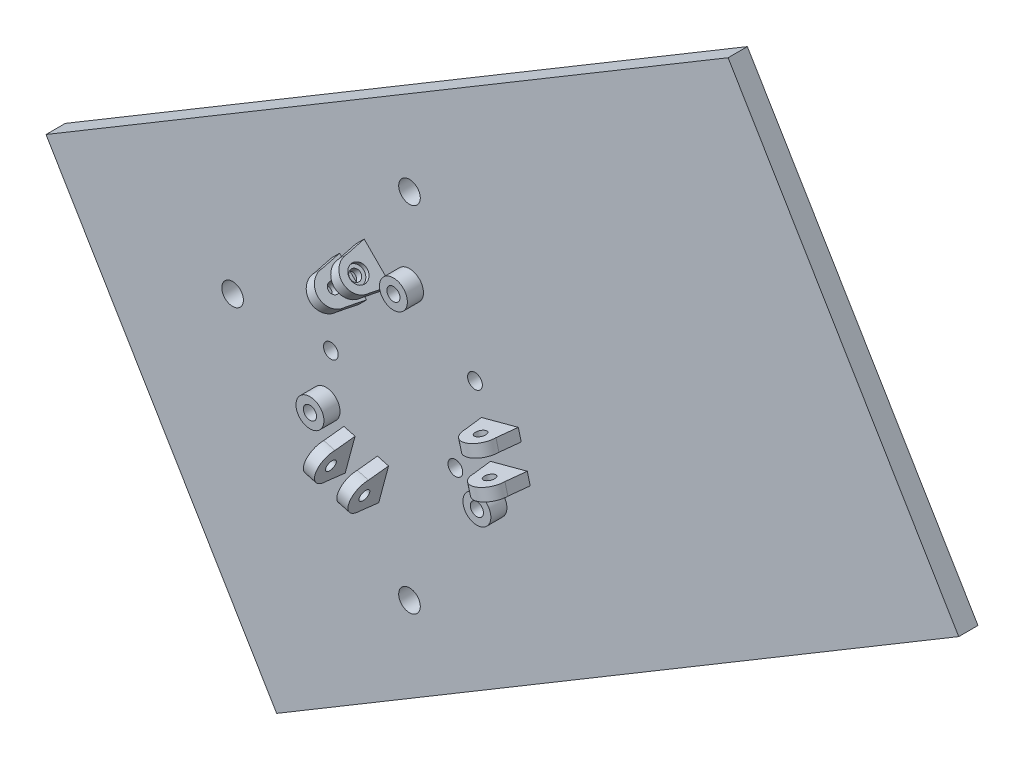
SolidWorks part; units mm, degrees
ref_plane "Front Plane" through (0, 0, 0) normal (0, 0, 1) x (1, 0, 0)
ref_plane "Top Plane" through (0, 0, 0) normal (0, 1, 0) x (1, 0, 0)
ref_plane "Right Plane" through (0, 0, 0) normal (1, 0, 0) x (0, 0, -1)
sketch "S01 - Rounded V3 backplate with cage and cassette fixings" plane through (0, 0, 0) normal (0, 0, 1) x (1, 0, 0)
  line L0 (-113.1634, 13.9297) -> (41.3567, 106.2526)
  line L5 (-113.1634, 13.9297) -> (-41.3567, -106.2526)
  line L7 (-41.3567, -106.2526) -> (113.1634, -13.9297)
  line L8 (-113.1634, 13.9297) -> (113.1634, -13.9297) construction
  line L9 (41.3567, 106.2526) -> (-41.3567, -106.2526) construction
  line L10 (41.3567, 106.2526) -> (99.1896, 140.8067)
  line L11 (99.1896, 140.8067) -> (170.9963, 20.6243)
  line L12 (170.9963, 20.6243) -> (113.1634, -13.9297)
  circle A7 centre (0, 55.0653) radius 3.3651
  circle A8 centre (-55.0653, 0) radius 3.3651
  circle A9 centre (0, -55.0653) radius 3.3651
  circle A10 centre (14.2762, -12.2367) radius 2.2944
  circle A11 centre (20.3946, 14.2762) radius 2.2944
  circle A12 centre (-24.4735, 0) radius 2.2944
  point P1 (0, 0)
  point P3 (0, 0)
  dimension "D2" = 180
  dimension "D3" = 55.0653
  dimension "D4" = 6.7302
  dimension "D5" = 4.5888
  dimension "D6" = 20.3946
  dimension "D7" = 14.2762
  dimension "D8" = 4.5888
  dimension "D9" = 14.2762
  dimension "D10" = 12.2367
  dimension "D11" = 24.4735
  dimension "D12" = 4.5888
  dimension "D13" = 30.5918
  dimension "D14" = 6.7302
  dimension "D16" = 6.7302
  dimension "D15" = 55.0653
  dimension "D17" = 140
  dimension "D18" = 113.1634
  dimension "D19" = 106.2526
  dimension "D20" = 67.3693
extrude "01 - Rounded V3 backplate with cage and cassette fixings" add sketch "S01 - Rounded V3 backplate with cage and cassette fixings" along normal blind 6 from offset 12 offset against normal yes
sketch "S02 - Three cord guide pedestals" plane through (0, 0, 0) normal (0, 0, 1) x (1, 0, 0)
  circle A0 centre (25.9808, -15) radius 4.35
  circle A1 centre (0, 30) radius 4.35
  circle A2 centre (-25.9808, -15) radius 4.35
  dimension "D1" = 8.7
  dimension "D2" = 8.7
  dimension "D3" = 8.7
  dimension "D4" = 25.9808
  dimension "D5" = 25.9808
  dimension "D6" = 30
  dimension "D7" = 15
extrude "02 - Three cord guide pedestals" add sketch "S02 - Three cord guide pedestals" along normal blind 5 from offset 6 offset against normal yes
sketch "S03 - Three smooth grommet seats" plane through (0, 0, 0) normal (0, 0, 1) x (1, 0, 0)
  circle A0 centre (25.9808, -15) radius 2.05
  circle A1 centre (0, 30) radius 2.05
  circle A2 centre (-25.9808, -15) radius 2.05
  dimension "D1" = 4.1
  dimension "D2" = 4.1
  dimension "D3" = 4.1
  dimension "D4" = 25.9808
  dimension "D5" = 25.9808
  dimension "D6" = 30
  dimension "D7" = 15
extrude "03 - Three smooth grommet seats" cut sketch "S03 - Three smooth grommet seats" along normal blind 14 from offset 13 offset against normal yes
sketch3d "Plane points - Integral A1 fork cheek L"
  point P0 (30, 0, 0)
  point P1 (12.6133, -4.6587, 0)
  point P2 (30, 0, 18)
ref_plane "Drilling plane - Integral A1 fork cheek L" through (2.0096, -7.5, 0) normal (-0.2588, 0.9659, 0) x (0.9659, 0.2588, 0)
sketch "S04 - Integral A1 fork cheek L" plane through (2.0096, -7.5, 0) normal (-0.2588, 0.9659, 0) x (0.9659, 0.2588, 0)
  line L0 (35.0778, 7) -> (22.8778, 7)
  line L1 (22.8778, 7) -> (24.0278, 0)
  line L2 (33.9278, 0) -> (35.0778, 7)
  arc A0 (24.0278, 0) -> (33.9278, 0) centre (28.9778, 0) ccw
  dimension "D1" = 4.95
  dimension "D2" = 22.8778
  dimension "D3" = 28.9778
  dimension "D4" = 35.0778
  dimension "D5" = 7
extrude "04 - Integral A1 fork cheek L" add sketch "S04 - Integral A1 fork cheek L" along normal blind 3.6 from offset 7.2 offset against normal yes
sketch3d "Plane points - Integral A1 fork cheek R"
  point P0 (30, 0, 0)
  point P1 (12.6133, -4.6587, 0)
  point P2 (30, 0, 18)
ref_plane "Drilling plane - Integral A1 fork cheek R" through (2.0096, -7.5, 0) normal (-0.2588, 0.9659, 0) x (0.9659, 0.2588, 0)
sketch "S05 - Integral A1 fork cheek R" plane through (2.0096, -7.5, 0) normal (-0.2588, 0.9659, 0) x (0.9659, 0.2588, 0)
  line L0 (35.0778, 7) -> (22.8778, 7)
  line L1 (22.8778, 7) -> (24.0278, 0)
  line L2 (33.9278, 0) -> (35.0778, 7)
  arc A0 (24.0278, 0) -> (33.9278, 0) centre (28.9778, 0) ccw
  dimension "D1" = 4.95
  dimension "D2" = 22.8778
  dimension "D3" = 28.9778
  dimension "D4" = 35.0778
  dimension "D5" = 7
extrude "05 - Integral A1 fork cheek R" add sketch "S05 - Integral A1 fork cheek R" along normal blind 3.6 from offset 3.6
sketch3d "Plane points - A1 pivot through both cheeks"
  point P0 (30, 0, 0)
  point P1 (12.6133, -4.6587, 0)
  point P2 (30, 0, 18)
ref_plane "Drilling plane - A1 pivot through both cheeks" through (2.0096, -7.5, 0) normal (-0.2588, 0.9659, 0) x (0.9659, 0.2588, 0)
sketch "S06 - A1 pivot through both cheeks" plane through (2.0096, -7.5, 0) normal (-0.2588, 0.9659, 0) x (0.9659, 0.2588, 0)
  circle A0 centre (28.9778, 0) radius 1.65
  dimension "D1" = 3.3
  dimension "D2" = 28.9778
extrude "06 - A1 pivot through both cheeks" cut sketch "S06 - A1 pivot through both cheeks" along normal blind 15 from offset 7.5 offset against normal yes
sketch3d "Plane points - A1 recessed pivot screw head"
  point P0 (30, 0, 0)
  point P1 (12.6133, -4.6587, 0)
  point P2 (30, 0, 18)
ref_plane "Drilling plane - A1 recessed pivot screw head" through (2.0096, -7.5, 0) normal (-0.2588, 0.9659, 0) x (0.9659, 0.2588, 0)
sketch "S07 - A1 recessed pivot screw head" plane through (2.0096, -7.5, 0) normal (-0.2588, 0.9659, 0) x (0.9659, 0.2588, 0)
  circle A0 centre (28.9778, 0) radius 2.7
  dimension "D1" = 5.4
  dimension "D2" = 28.9778
extrude "07 - A1 recessed pivot screw head" cut sketch "S07 - A1 recessed pivot screw head" along normal blind 1.5 from offset 7.3 offset against normal yes
sketch3d "Plane points - Integral A2 fork cheek L"
  point P0 (-15, 25.9808, 0)
  point P1 (-2.2721, 13.2528, 0)
  point P2 (-15, 25.9808, 18)
ref_plane "Drilling plane - Integral A2 fork cheek L" through (5.4904, 5.4904, 0) normal (-0.7071, -0.7071, 0) x (-0.7071, 0.7071, 0)
sketch "S08 - Integral A2 fork cheek L" plane through (5.4904, 5.4904, 0) normal (-0.7071, -0.7071, 0) x (-0.7071, 0.7071, 0)
  line L0 (35.0778, 7) -> (22.8778, 7)
  line L1 (22.8778, 7) -> (24.0278, 0)
  line L2 (33.9278, 0) -> (35.0778, 7)
  arc A0 (24.0278, 0) -> (33.9278, 0) centre (28.9778, 0) ccw
  dimension "D1" = 4.95
  dimension "D2" = 22.8778
  dimension "D3" = 28.9778
  dimension "D4" = 35.0778
  dimension "D5" = 7
extrude "08 - Integral A2 fork cheek L" add sketch "S08 - Integral A2 fork cheek L" along normal blind 3.6 from offset 7.2 offset against normal yes
sketch3d "Plane points - Integral A2 fork cheek R"
  point P0 (-15, 25.9808, 0)
  point P1 (-2.2721, 13.2528, 0)
  point P2 (-15, 25.9808, 18)
ref_plane "Drilling plane - Integral A2 fork cheek R" through (5.4904, 5.4904, 0) normal (-0.7071, -0.7071, 0) x (-0.7071, 0.7071, 0)
sketch "S09 - Integral A2 fork cheek R" plane through (5.4904, 5.4904, 0) normal (-0.7071, -0.7071, 0) x (-0.7071, 0.7071, 0)
  line L0 (35.0778, 7) -> (22.8778, 7)
  line L1 (22.8778, 7) -> (24.0278, 0)
  line L2 (33.9278, 0) -> (35.0778, 7)
  arc A0 (24.0278, 0) -> (33.9278, 0) centre (28.9778, 0) ccw
  dimension "D1" = 4.95
  dimension "D2" = 22.8778
  dimension "D3" = 28.9778
  dimension "D4" = 35.0778
  dimension "D5" = 7
extrude "09 - Integral A2 fork cheek R" add sketch "S09 - Integral A2 fork cheek R" along normal blind 3.6 from offset 3.6
sketch3d "Plane points - A2 pivot through both cheeks"
  point P0 (-15, 25.9808, 0)
  point P1 (-2.2721, 13.2528, 0)
  point P2 (-15, 25.9808, 18)
ref_plane "Drilling plane - A2 pivot through both cheeks" through (5.4904, 5.4904, 0) normal (-0.7071, -0.7071, 0) x (-0.7071, 0.7071, 0)
sketch "S10 - A2 pivot through both cheeks" plane through (5.4904, 5.4904, 0) normal (-0.7071, -0.7071, 0) x (-0.7071, 0.7071, 0)
  circle A0 centre (28.9778, 0) radius 1.65
  dimension "D1" = 3.3
  dimension "D2" = 28.9778
extrude "10 - A2 pivot through both cheeks" cut sketch "S10 - A2 pivot through both cheeks" along normal blind 15 from offset 7.5 offset against normal yes
sketch3d "Plane points - A2 recessed pivot screw head"
  point P0 (-15, 25.9808, 0)
  point P1 (-2.2721, 13.2528, 0)
  point P2 (-15, 25.9808, 18)
ref_plane "Drilling plane - A2 recessed pivot screw head" through (5.4904, 5.4904, 0) normal (-0.7071, -0.7071, 0) x (-0.7071, 0.7071, 0)
sketch "S11 - A2 recessed pivot screw head" plane through (5.4904, 5.4904, 0) normal (-0.7071, -0.7071, 0) x (-0.7071, 0.7071, 0)
  circle A0 centre (28.9778, 0) radius 2.7
  dimension "D1" = 5.4
  dimension "D2" = 28.9778
extrude "11 - A2 recessed pivot screw head" cut sketch "S11 - A2 recessed pivot screw head" along normal blind 1.5 from offset 7.3 offset against normal yes
sketch3d "Plane points - Integral A3 fork cheek L"
  point P0 (-15, -25.9808, 0)
  point P1 (-10.3413, -8.5941, 0)
  point P2 (-15, -25.9808, 18)
ref_plane "Drilling plane - Integral A3 fork cheek L" through (-7.5, 2.0096, 0) normal (0.9659, -0.2588, 0) x (0, 0, -1)
sketch "S12 - Integral A3 fork cheek L" plane through (-7.5, 2.0096, 0) normal (0.9659, -0.2588, 0) x (0, 0, -1)
  line L0 (7, -35.0778) -> (7, -22.8778)
  line L1 (7, -22.8778) -> (0, -24.0278)
  line L2 (0, -33.9278) -> (7, -35.0778)
  arc A0 (0, -24.0278) -> (0, -33.9278) centre (0, -28.9778) ccw
  dimension "D1" = 4.95
  dimension "D2" = 7
  dimension "D3" = 22.8778
  dimension "D4" = 28.9778
  dimension "D5" = 35.0778
extrude "12 - Integral A3 fork cheek L" add sketch "S12 - Integral A3 fork cheek L" along normal blind 3.6 from offset 7.2 offset against normal yes
sketch3d "Plane points - Integral A3 fork cheek R"
  point P0 (-15, -25.9808, 0)
  point P1 (-10.3413, -8.5941, 0)
  point P2 (-15, -25.9808, 18)
ref_plane "Drilling plane - Integral A3 fork cheek R" through (-7.5, 2.0096, 0) normal (0.9659, -0.2588, 0) x (0, 0, -1)
sketch "S13 - Integral A3 fork cheek R" plane through (-7.5, 2.0096, 0) normal (0.9659, -0.2588, 0) x (0, 0, -1)
  line L0 (7, -35.0778) -> (7, -22.8778)
  line L1 (7, -22.8778) -> (0, -24.0278)
  line L2 (0, -33.9278) -> (7, -35.0778)
  arc A0 (0, -24.0278) -> (0, -33.9278) centre (0, -28.9778) ccw
  dimension "D1" = 4.95
  dimension "D2" = 7
  dimension "D3" = 22.8778
  dimension "D4" = 28.9778
  dimension "D5" = 35.0778
extrude "13 - Integral A3 fork cheek R" add sketch "S13 - Integral A3 fork cheek R" along normal blind 3.6 from offset 3.6
sketch3d "Plane points - A3 pivot through both cheeks"
  point P0 (-15, -25.9808, 0)
  point P1 (-10.3413, -8.5941, 0)
  point P2 (-15, -25.9808, 18)
ref_plane "Drilling plane - A3 pivot through both cheeks" through (-7.5, 2.0096, 0) normal (0.9659, -0.2588, 0) x (0, 0, -1)
sketch "S14 - A3 pivot through both cheeks" plane through (-7.5, 2.0096, 0) normal (0.9659, -0.2588, 0) x (0, 0, -1)
  circle A0 centre (0, -28.9778) radius 1.65
  dimension "D1" = 3.3
  dimension "D2" = 28.9778
extrude "14 - A3 pivot through both cheeks" cut sketch "S14 - A3 pivot through both cheeks" along normal blind 15 from offset 7.5 offset against normal yes
sketch3d "Plane points - A3 recessed pivot screw head"
  point P0 (-15, -25.9808, 0)
  point P1 (-10.3413, -8.5941, 0)
  point P2 (-15, -25.9808, 18)
ref_plane "Drilling plane - A3 recessed pivot screw head" through (-7.5, 2.0096, 0) normal (0.9659, -0.2588, 0) x (0, 0, -1)
sketch "S15 - A3 recessed pivot screw head" plane through (-7.5, 2.0096, 0) normal (0.9659, -0.2588, 0) x (0, 0, -1)
  circle A0 centre (0, -28.9778) radius 2.7
  dimension "D1" = 5.4
  dimension "D2" = 28.9778
extrude "15 - A3 recessed pivot screw head" cut sketch "S15 - A3 recessed pivot screw head" along normal blind 1.5 from offset 7.3 offset against normal yes
